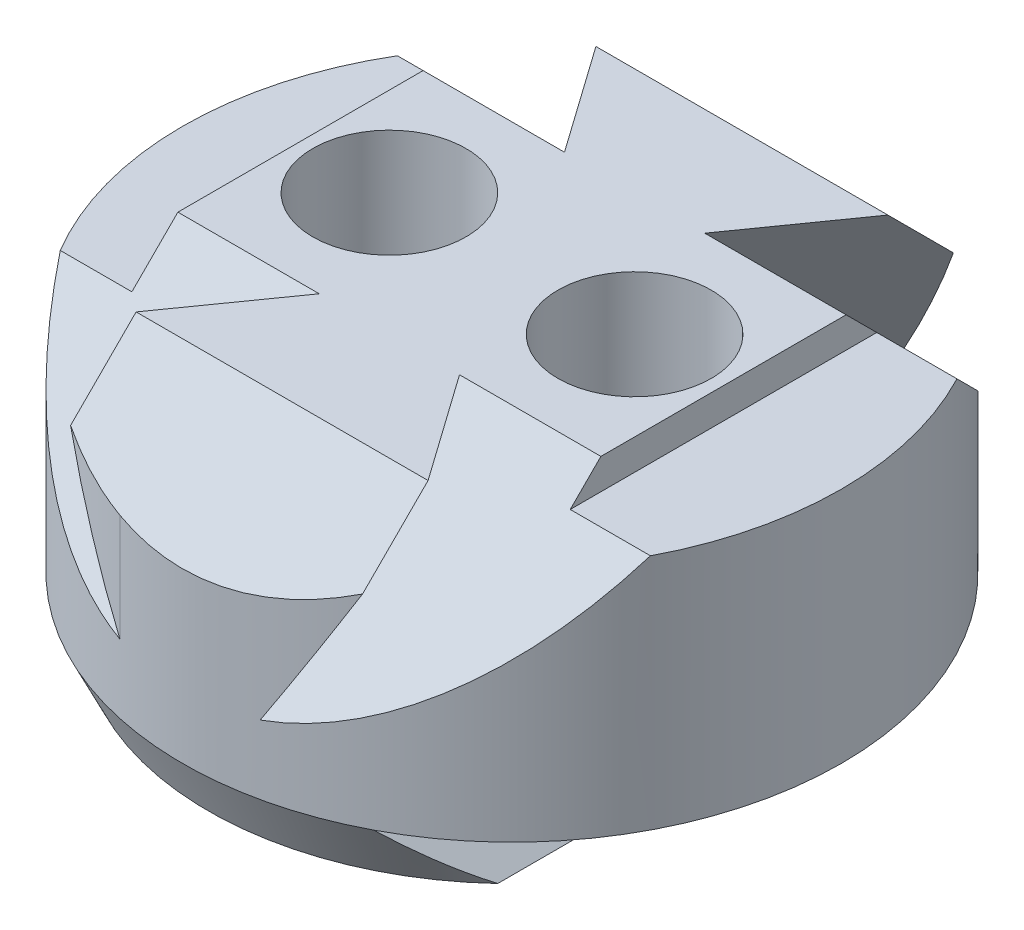
SolidWorks part; units mm, degrees
ref_plane "Front Plane" through (0, 0, 0) normal (0, 0, 1) x (1, 0, 0)
ref_plane "Top Plane" through (0, 0, 0) normal (0, 1, 0) x (1, 0, 0)
ref_plane "Right Plane" through (0, 0, 0) normal (1, 0, 0) x (0, 0, -1)
sketch "Sketch1" plane through (0, 0, 0) normal (0, 1, 0) x (1, 0, 0)
  circle A0 centre (0, 0) radius 21.5
  dimension "D1" = 43
extrude "Boss-Extrude1" add sketch "Sketch1" against normal blind 4
sketch "Sketch2" plane through (0, 0, 0) normal (0, 1, 0) x (1, 0, 0)
  circle A0 centre (0, 0) radius 5.875
  dimension "D1" = 11.75
extrude "Boss-Extrude2" add sketch "Sketch2" along normal blind 65
sketch "Sketch3" plane through (0, 0, 0) normal (0, 1, 0) x (1, 0, 0)
  line L0 (0, 0) -> (0, 21.5) construction
  line L1 (0, 21.5) -> (0, -21.5) construction
  circle A0 centre (0, 0) radius 21.5 construction
ref_plane "Plane1" through (0, 15.5, 0) normal (0, 1, 0) x (1, 0, 0)
sketch "Sketch5" plane through (0, 0, 0) normal (1, 0, 0) x (0, 0, -1)
  line L4 (21.5, 0) -> (-21.5, 0) construction
  line L5 (6, 0) -> (0, 0) construction
  line L8 (21.5, 0) -> (0, 0)
  line L10 (-21.5, 0) -> (0, 0)
  line L11 (21.5, 0) -> (6, 15.5)
  line L12 (23.65, 15.5) -> (-23.65, 15.5) construction
  line L13 (6, 15.5) -> (-6, 15.5)
  line L14 (-6, 15.5) -> (-21.5, 0)
  dimension "D1" = 21.5
  dimension "D2" = 15.5
  dimension "D3" = 15.5
extrude "Boss-Extrude3" add sketch "Sketch5" along normal up to surface and the other way up to surface up to face at (0, -4, 21.5) other way up to face at (0, -4, 21.5)
ref_plane "Plane2" through (0, 4.75, -4.75) normal (0, 0.7071, -0.7071) x (-1, 0, 0)
ref_plane "Plane3" through (0, 4.75, 4.75) normal (0, -0.7071, -0.7071) x (-1, 0, 0)
sketch "Sketch6" plane through (0, 4.75, 4.75) normal (0, -0.7071, -0.7071) x (-1, 0, 0)
  line L0 (0, 15.2028) -> (4.5753, 15.2028)
  line L1 (20.6458, 15.2028) -> (-20.6458, 15.2028) construction
  line L2 (4.5753, 15.2028) -> (9.525, 20.1525)
  line L3 (9.525, 20.1525) -> (0, 20.1525)
  line L4 (0, 20.1525) -> (-9.525, 20.1525)
  line L5 (-9.525, 20.1525) -> (-4.5753, 15.2028)
  line L6 (-4.5753, 15.2028) -> (0, 15.2028)
  dimension "D1" = 7
  dimension "D2" = 45
  dimension "D3" = 45
  dimension "D4" = 9.525
ref_plane "Plane4" through (0, 0, 6) normal (0, 0, 1) x (1, 0, 0)
ref_plane "Plane5" through (0, 0, -6) normal (0, 0, 1) x (1, 0, 0)
sketch "Sketch10" plane through (0, 4.75, -4.75) normal (0, 0.7071, -0.7071) x (-1, 0, 0)
  line L14 (0, 15.2028) -> (-4.5753, 15.2028)
  line L15 (20.6458, 15.2028) -> (-20.6458, 15.2028) construction
  line L16 (-4.5753, 15.2028) -> (-9.525, 20.1525)
  line L18 (9.525, 20.1525) -> (4.5753, 15.2028)
  line L19 (4.5753, 15.2028) -> (0, 15.2028)
  line L20 (9.525, 20.1525) -> (0, 20.1525)
  line L21 (0, 20.1525) -> (-9.525, 20.1525)
  dimension "D1" = 45
  dimension "D2" = 9.525
  dimension "D3" = 7
  dimension "D4" = 45
sketch "Sketch11" plane through (0, 0, 6) normal (0, 0, 1) x (1, 0, 0)
  line L0 (0, 65) -> (0, 15.5) construction
  line L1 (5.875, 65) -> (-5.875, 65) construction
  line L2 (0, 65) -> (0, 15.5) construction
sketch "Sketch12" plane through (0, 15.5, 0) normal (0, 1, 0) x (1, 0, 0)
  line L0 (-20.6458, 6) -> (20.6458, 6)
  line L1 (20.6458, -6) -> (-20.6458, -6)
  arc A0 (-20.6458, 6) -> (-20.6458, -6) centre (0, 0) ccw
  arc A2 (20.6458, 6) -> (20.6458, -6) centre (0, 0) cw
extrude "Boss-Extrude12" add sketch "Sketch6" along normal up to surface (21.9203 mm away) contours L3 L4 L5 L6 L0 L2 up to face at (0, -4, 21.5)
sketch "Sketch14" plane through (0, 15.5, 0) normal (0, 1, 0) x (1, 0, 0)
  circle A0 centre (0, 0) radius 5.875
  dimension "D1" = 11.75
ref_plane "Plane7" through (0, -4, 0) normal (0, -1, 0) x (-1, 0, 0)
sketch "Sketch17" plane through (0, 0, 0) normal (0, 0, 1) x (1, 0, 0)
  line L1 (-23.65, -4) -> (23.65, -4) construction
  line L2 (0, -4) -> (5, -4)
  line L3 (0, -4) -> (0, 6)
  line L4 (0, 6) -> (5, -4)
revolve "Cut-Revolve1" cut sketch "Sketch17" angle 360 about L3
extrude "Boss-Extrude13" add sketch "Sketch10" against normal up to surface (13.8239 mm away) contours L21 L16 L14 L19 L18 L20 up to face at (0, -4, 21.5)
extrude "Cut-Extrude3" cut sketch "Sketch14" along normal blind 10 and the other way blind 2 flip side to cut contours A0
ref_plane "Plane8" through (0, 13.5, 0) normal (0, 1, 0) x (1, 0, 0)
sketch "Sketch18" plane through (0, 0, 0) normal (1, 0, 0) x (0, 0, -1)
  line L0 (0, -4) -> (21.5, -4)
  line L1 (-23.65, -4) -> (23.65, -4) construction
  line L2 (21.5, -4) -> (21.5, 7) construction
  line L3 (21.5, -4) -> (0, -49)
  line L4 (0, -49) -> (0, -4)
  dimension "D1" = 45
sketch "Sketch19" plane through (0, 13.5, 0) normal (0, 1, 0) x (1, 0, 0)
  line L0 (0, 0) -> (11, 0) construction
  line L1 (0, 21.5) -> (0, -21.5) construction
  line L2 (11, 0) -> (11, 8)
  line L3 (19.9562, 8) -> (4.5753, 8) construction
  line L4 (11, 0) -> (11, -8)
  line L5 (4.5753, -8) -> (19.9562, -8) construction
  line L6 (0, 0) -> (-11, 0) construction
  line L7 (-11, 0) -> (-11, 8)
  line L8 (-4.5753, 8) -> (-19.9562, 8) construction
  line L9 (-11, 0) -> (-11, -8)
  line L10 (-19.9562, -8) -> (-4.5753, -8) construction
sketch "Sketch20" plane through (0, 0, 0) normal (0, 0, 1) x (1, 0, 0)
  line L0 (0, 13.5) -> (0, 25.5)
  line L1 (0, 13.5) -> (-11, 13.5) construction
  line L2 (0, 13.5) -> (11, 13.5) construction
  line L3 (0, 65) -> (0, 15.5) construction
  line L4 (0, 25.5) -> (-11, 13.5)
  line L5 (0, 25.5) -> (11, 13.5)
  line L6 (-5.875, 65) -> (-5.875, 13.5) construction
  line L7 (5.875, 13.5) -> (5.875, 65) construction
  line L8 (11, 13.5) -> (21.5, 2.0455)
  line L9 (21.5, -4) -> (21.5, 13.5) construction
  point P11 (-5.875, 19.0909)
  point P15 (5.875, 19.0909)
ref_plane "Plane9" through (0, 13.5, 0) normal (-0.6757, -0.7372, 0) x (0, 0, 1)
ref_plane "Plane10" through (0, 13.5, 0) normal (0.6757, -0.7372, 0) x (0, 0, -1)
ref_plane "Plane11" through (6.8269, 7.4475, 0) normal (-0.6757, -0.7372, 0) x (0, 0, 1)
sketch "Sketch22" plane through (6.8269, 7.4475, 0) normal (-0.6757, -0.7372, 0) x (0, 0, 1)
  line L0 (0, 17.231) -> (15, 17.231)
  line L1 (15, 17.231) -> (15, 27.3886)
  line L2 (15, 27.3886) -> (-15, 27.3886)
  line L3 (-15, 27.3886) -> (-15, 17.231)
  line L4 (-15, 17.231) -> (0, 17.231)
ref_plane "Plane12" through (-6.8269, 7.4475, 0) normal (0.6757, -0.7372, 0) x (-0.7372, -0.6757, 0)
sketch "Sketch23" plane through (-6.8269, 7.4475, 0) normal (0.6757, -0.7372, 0) x (-0.7372, -0.6757, 0)
  line L0 (-17.231, 0) -> (-17.231, 15)
  line L1 (-17.231, 15) -> (-27.231, 15)
  line L2 (-27.231, 15) -> (-27.231, -15)
  line L3 (-27.231, -15) -> (-17.231, -15)
  line L4 (-17.231, -15) -> (-17.231, 0)
sketch "Sketch24" plane through (0, 0, 0) normal (0, 0, 1) x (1, 0, 0)
  line L0 (0, -4) -> (10, -4)
  line L1 (0, -4) -> (0, -49) construction
  line L2 (0, -49) -> (0, -4) construction
  line L3 (-23.65, -4) -> (23.65, -4) construction
  line L4 (10, -4) -> (13.5355, -7.5355)
  line L6 (0, -4) -> (-10, -4)
  line L7 (-10, -4) -> (-13.5355, -7.5355)
  line L8 (-13.5355, -7.5355) -> (13.5355, -7.5355)
  dimension "D1" = 10
  dimension "D2" = 10
  dimension "D3" = 5
  dimension "D4" = 45
  dimension "D5" = 5
extrude "Boss-Extrude15" add sketch "Sketch24" along normal up to surface and the other way up to surface up to face at (0, -4, 21.5) other way up to face at (0, -4, 21.5)
sketch "Sketch25" plane through (0, 0, 0) normal (1, 0, 0) x (0, 0, -1)
  line L0 (21.5, -4) -> (21.5, -7.5355)
  line L1 (21.5, -7.5355) -> (19.8108, -7.5355)
  line L2 (21.5, -4) -> (0, -49) construction
  line L3 (16.7045, -7.5355) -> (21.5, -7.5355) construction
  line L4 (19.8108, -7.5355) -> (21.5, -4)
  line L5 (0, -4) -> (0, -7.5355) construction
  line L6 (-16.7045, -7.5355) -> (16.7045, -7.5355) construction
revolve "Cut-Revolve2" cut sketch "Sketch25" angle 360 about L5
sketch "Sketch29" plane through (0, 65, 0) normal (0, 1, 0) x (1, 0, 0)
  circle A0 centre (0, 0) radius 7.5081
  dimension "D1" = 15.0162
extrude "Cut-Extrude9" cut sketch "Sketch29" along direction (0, 1, 0) on the side against the normal up to surface (51.5 mm away) up to face at (0, 13.5, 5.875)
sketch "Sketch30" plane through (0, 13.5, 0) normal (0, 1, 0) x (1, 0, 0)
  line L0 (-23.65, 0) -> (23.65, 0) construction
  circle A0 centre (-8, 0) radius 5
  circle A1 centre (8, 0) radius 5
  dimension "D1" = 10
  dimension "D2" = 10
  dimension "D3" = 8
  dimension "D4" = 8
extrude "Cut-Extrude10" cut sketch "Sketch30" against normal blind 12
sketch "Sketch31" plane through (0, 0, -6) normal (0, 0, 1) x (1, 0, 0)
  line L0 (-19.9562, 13.5) -> (-21.5, 13.5) construction
  line L1 (21.5, 13.5) -> (13.8, 13.5)
  line L2 (21.5, 13.5) -> (21.5, 11.5)
  line L3 (21.5, 11.5) -> (13.8, 11.5)
  line L4 (13.8, 13.5) -> (13.8, 11.5)
  line L5 (-21.5, 13.5) -> (-13.8, 13.5)
  line L6 (-21.5, 13.5) -> (-21.5, 10.5)
  line L7 (-21.5, 10.5) -> (-13.8, 10.5)
  line L8 (-13.8, 13.5) -> (-13.8, 10.5)
  dimension "D1" = 7.7
  dimension "D2" = 2
  dimension "D3" = 7.7
  dimension "D4" = 3
extrude "Cut-Extrude13" cut sketch "Sketch31" against normal through all both and the other way through all
sketch "Sketch32" plane through (0, 13.5, 0) normal (0, 1, 0) x (1, 0, 0)
  line L1 (-1.3, 8) -> (1.3, 8)
  line L2 (-1.3, 8) -> (-1.3, -8)
  line L3 (-1.3, -8) -> (1.3, -8)
  line L4 (1.3, 8) -> (1.3, -8)
  line L5 (-1.3, 8) -> (1.3, -8) construction
  line L6 (-1.3, -8) -> (1.3, 8) construction
  point P0 (0, 0)
  dimension "D1" = 16
  dimension "D2" = 2.6
